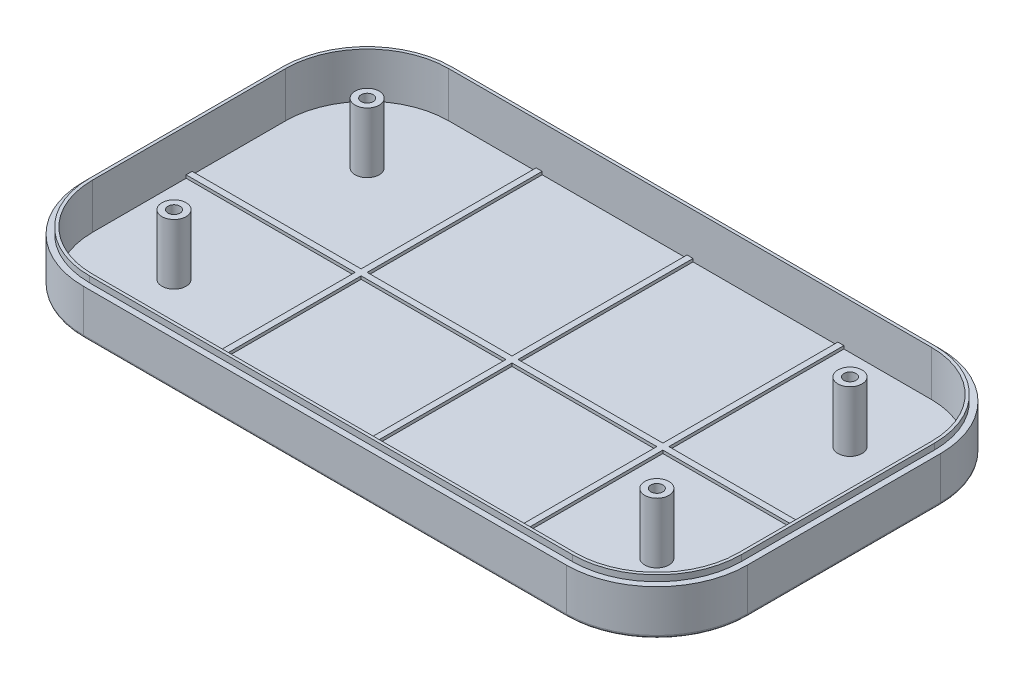
SolidWorks part; units mm, degrees
ref_plane "Front Plane" through (0, 0, 0) normal (0, 0, 1) x (1, 0, 0)
ref_plane "Top Plane" through (0, 0, 0) normal (0, 1, 0) x (1, 0, 0)
ref_plane "Right Plane" through (0, 0, 0) normal (1, 0, 0) x (0, 0, -1)
sketch "Sketch1" plane through (0, 0, 0) normal (0, 1, 0) x (1, 0, 0)
  line L1 (-80, 62) -> (80, 62)
  line L2 (-110, 32) -> (-110, -32)
  line L3 (-80, -62) -> (80, -62)
  line L4 (110, 32) -> (110, -32)
  line L5 (-110, 62) -> (110, -62) construction
  line L6 (-110, -62) -> (110, 62) construction
  arc A0 (-110, -32) -> (-80, -62) centre (-80, -32) ccw
  arc A1 (80, -62) -> (110, -32) centre (80, -32) ccw
  arc A2 (80, 62) -> (110, 32) centre (80, 32) cw
  arc A3 (-80, 62) -> (-110, 32) centre (-80, 32) ccw
  point P0 (0, 0)
  dimension "D3" = 30
  dimension "D1" = 220
  dimension "D2" = 124
extrude "Boss-Extrude1" add sketch "Sketch1" along normal blind 15
sketch "Sketch2" plane through (0, 15, 0) normal (0, 1, 0) x (1, 0, 0)
  line L8 (-80, -60) -> (80, -60)
  line L9 (108, -32) -> (108, 32)
  line L10 (80, 60) -> (-80, 60)
  line L11 (-108, 32) -> (-108, -32)
  line L12 (-80, -60) -> (80, -60)
  line L13 (108, -32) -> (108, 32)
  line L14 (80, 60) -> (-80, 60)
  line L15 (-108, 32) -> (-108, -32)
  arc A8 (-108, -32) -> (-80, -60) centre (-80, -32) ccw
  arc A9 (80, -60) -> (108, -32) centre (80, -32) ccw
  arc A10 (108, 32) -> (80, 60) centre (80, 32) ccw
  arc A11 (-80, 60) -> (-108, 32) centre (-80, 32) ccw
  arc A12 (-108, -32) -> (-80, -60) centre (-80, -32) ccw
  arc A13 (80, -60) -> (108, -32) centre (80, -32) ccw
  arc A14 (108, 32) -> (80, 60) centre (80, 32) ccw
  arc A15 (-80, 60) -> (-108, 32) centre (-80, 32) ccw
  dimension "D1" = 2
extrude "Cut-Extrude1" cut sketch "Sketch2" against normal blind 13
sketch "Sketch3" plane through (0, 2, 0) normal (0, 1, 0) x (1, 0, 0)
  line L8 (-80, -59) -> (80, -59)
  line L9 (107, -32) -> (107, 32)
  line L10 (80, 59) -> (-80, 59)
  line L11 (-107, 32) -> (-107, -32)
  line L12 (-80, -59) -> (80, -59)
  line L13 (107, -32) -> (107, 32)
  line L14 (80, 59) -> (-80, 59)
  line L15 (-107, 32) -> (-107, -32)
  line L20 (-80, -60) -> (80, -60)
  line L21 (108, -32) -> (108, 32)
  line L22 (80, 60) -> (-80, 60)
  line L23 (-108, 32) -> (-108, -32)
  line L24 (-80, -60) -> (80, -60)
  line L25 (108, -32) -> (108, 32)
  line L26 (80, 60) -> (-80, 60)
  line L27 (-108, 32) -> (-108, -32)
  arc A8 (-107, -32) -> (-80, -59) centre (-80, -32) ccw
  arc A9 (80, -59) -> (107, -32) centre (80, -32) ccw
  arc A10 (107, 32) -> (80, 59) centre (80, 32) ccw
  arc A11 (-80, 59) -> (-107, 32) centre (-80, 32) ccw
  arc A12 (-107, -32) -> (-80, -59) centre (-80, -32) ccw
  arc A13 (80, -59) -> (107, -32) centre (80, -32) ccw
  arc A14 (107, 32) -> (80, 59) centre (80, 32) ccw
  arc A15 (-80, 59) -> (-107, 32) centre (-80, 32) ccw
  arc A20 (-108, -32) -> (-80, -60) centre (-80, -32) ccw
  arc A21 (80, -60) -> (108, -32) centre (80, -32) ccw
  arc A22 (108, 32) -> (80, 60) centre (80, 32) ccw
  arc A23 (-80, 60) -> (-108, 32) centre (-80, 32) ccw
  arc A24 (-108, -32) -> (-80, -60) centre (-80, -32) ccw
  arc A25 (80, -60) -> (108, -32) centre (80, -32) ccw
  arc A26 (108, 32) -> (80, 60) centre (80, 32) ccw
  arc A27 (-80, 60) -> (-108, 32) centre (-80, 32) ccw
  dimension "D1" = 1
  dimension "D2" = 0
extrude "Boss-Extrude2" add sketch "Sketch3" along normal blind 15
sketch "Sketch5" plane through (0, 0, 0) normal (0, -1, 0) x (1, 0, 0)
  line L8 (-88, 32) -> (-88, -32)
  line L9 (-80, -40) -> (80, -40)
  line L10 (88, -32) -> (88, 32)
  line L11 (80, 40) -> (-80, 40)
  line L12 (-88, 32) -> (-88, 20)
  line L13 (-80, -40) -> (-68, -40)
  line L14 (88, -32) -> (88, -20)
  line L15 (80, 40) -> (68, 40)
  line L16 (68, -40) -> (80, -40)
  line L17 (-88, -20) -> (-88, -32)
  line L18 (68, 42) -> (68, 40)
  line L19 (90, 20) -> (88, 20)
  line L20 (-90, 32) -> (-90, -32)
  line L21 (-80, -42) -> (80, -42)
  line L22 (90, -32) -> (90, 32)
  line L23 (80, 42) -> (-80, 42)
  line L24 (-90, 32) -> (-90, 20)
  line L25 (-80, -42) -> (-68, -42)
  line L26 (90, -32) -> (90, -20)
  line L27 (80, 42) -> (68, 42)
  line L28 (90, -20) -> (88, -20)
  line L29 (68, -40) -> (68, -42)
  line L30 (-68, 42) -> (-68, 40)
  line L31 (-90, 20) -> (-88, 20)
  line L32 (-68, -40) -> (-68, -42)
  line L33 (-90, -20) -> (-88, -20)
  line L34 (-68, 42) -> (-80, 42)
  line L35 (-68, 40) -> (-80, 40)
  line L36 (68, -42) -> (80, -42)
  line L37 (90, 20) -> (90, 32)
  line L38 (88, 20) -> (88, 32)
  line L39 (-90, -20) -> (-90, -32)
  arc A8 (-80, 40) -> (-88, 32) centre (-80, 32) ccw
  arc A9 (-88, -32) -> (-80, -40) centre (-80, -32) ccw
  arc A10 (80, -40) -> (88, -32) centre (80, -32) ccw
  arc A11 (88, 32) -> (80, 40) centre (80, 32) ccw
  arc A12 (-80, 40) -> (-88, 32) centre (-80, 32) ccw
  arc A13 (-88, -32) -> (-80, -40) centre (-80, -32) ccw
  arc A14 (80, -40) -> (88, -32) centre (80, -32) ccw
  arc A15 (88, 32) -> (80, 40) centre (80, 32) ccw
  arc A20 (-80, 42) -> (-90, 32) centre (-80, 32) ccw
  arc A21 (-90, -32) -> (-80, -42) centre (-80, -32) ccw
  arc A22 (80, -42) -> (90, -32) centre (80, -32) ccw
  arc A23 (90, 32) -> (80, 42) centre (80, 32) ccw
  arc A24 (-80, 42) -> (-90, 32) centre (-80, 32) ccw
  arc A25 (-90, -32) -> (-80, -42) centre (-80, -32) ccw
  arc A26 (80, -42) -> (90, -32) centre (80, -32) ccw
  arc A27 (90, 32) -> (80, 42) centre (80, 32) ccw
  point P35 (68, 0)
  dimension "D3" = 20
  dimension "D1" = 22
  dimension "D2" = 20
extrude "Boss-Extrude3" add sketch "Sketch5" along normal blind 2
sketch "Sketch6" plane through (0, 2, 0) normal (0, 1, 0) x (1, 0, 0)
  circle A1 centre (80, 32) radius 4
  circle A2 centre (80, -32) radius 4
  circle A3 centre (-80, -32) radius 4
  circle A4 centre (-80, 32) radius 4
  dimension "D1" = 8
extrude "Boss-Extrude4" add sketch "Sketch6" along normal blind 20
sketch "Sketch7" plane through (0, 22, 0) normal (0, 1, 0) x (1, 0, 0)
  line L0 (107, 0) -> (81.6257, 0)
  line L1 (107, -32) -> (107, 32) construction
  line L2 (0, 7.0485) -> (0, 59)
  line L3 (80, 59) -> (-80, 59) construction
  circle A0 centre (80, 32) radius 2
  circle A1 centre (80, -32) radius 2
  circle A2 centre (-80, -32) radius 2
  circle A3 centre (-80, 32) radius 2
  dimension "D1" = 4
extrude "Cut-Extrude2" cut sketch "Sketch7" against normal blind 54 contours A3 | A2 | A0 | A1
sketch "Sketch8" plane through (0, 0, 0) normal (0, -1, 0) x (1, 0, 0)
  circle A0 centre (-80, 32) radius 3.5
  circle A1 centre (-80, -32) radius 3.5
  circle A2 centre (80, -32) radius 3.5
  circle A3 centre (80, 32) radius 3.5
  dimension "D1" = 7
extrude "Cut-Extrude3" cut sketch "Sketch8" against normal blind 10
sketch "Sketch9" plane through (0, 2, 0) normal (0, 1, 0) x (1, 0, 0)
  line L0 (49, -59) -> (51, -59)
  line L4 (49, -1) -> (49, -59)
  line L6 (-1, -59) -> (1, -59)
  line L9 (-49, 59) -> (-51, 59)
  line L10 (-49, -1) -> (-49, -59)
  line L13 (1, 59) -> (-1, 59)
  line L14 (-1, 1) -> (-49, 1)
  line L15 (-51, 59) -> (-51, 1)
  line L16 (-80, -59) -> (80, -59)
  line L17 (107, -32) -> (107, 32)
  line L18 (80, 59) -> (-80, 59)
  line L19 (-107, 32) -> (-107, -32)
  line L20 (-51, -59) -> (-49, -59)
  line L21 (107, -1) -> (107, 1)
  line L22 (51, 59) -> (49, 59)
  line L23 (-107, 1) -> (-107, -1)
  line L24 (-1, 59) -> (-1, 1)
  line L25 (-1, -1) -> (-1, -59)
  line L26 (49, 59) -> (49, 1)
  line L27 (1, -1) -> (49, -1)
  line L28 (-1, -1) -> (-49, -1)
  line L29 (-49, 59) -> (-49, 1)
  line L30 (1, 59) -> (1, 1)
  line L31 (1, -1) -> (1, -59)
  line L32 (51, 59) -> (51, 1)
  line L33 (1, 1) -> (49, 1)
  line L34 (-51, -1) -> (-107, -1)
  line L38 (51, -1) -> (51, -59)
  line L39 (-51, -1) -> (-51, -59)
  line L41 (-51, 1) -> (-107, 1)
  line L42 (51, -1) -> (107, -1)
  line L44 (51, 1) -> (107, 1)
  arc A8 (-107, -32) -> (-80, -59) centre (-80, -32) ccw
  arc A9 (80, -59) -> (107, -32) centre (80, -32) ccw
  arc A10 (107, 32) -> (80, 59) centre (80, 32) ccw
  arc A11 (-80, 59) -> (-107, 32) centre (-80, 32) ccw
  dimension "D1" = 0
extrude "Boss-Extrude5" add sketch "Sketch9" along normal blind 1
fillet "Fillet1" radius 1 8 edges at (-101.2132, 0, -53.2132) (0, 0, -62) (101.2132, 0, -53.2132) (110, 0, 0) (101.2132, 0, 53.2132) (0, 0, 62) (-101.2132, 0, 53.2132) (-110, 0, 0)
